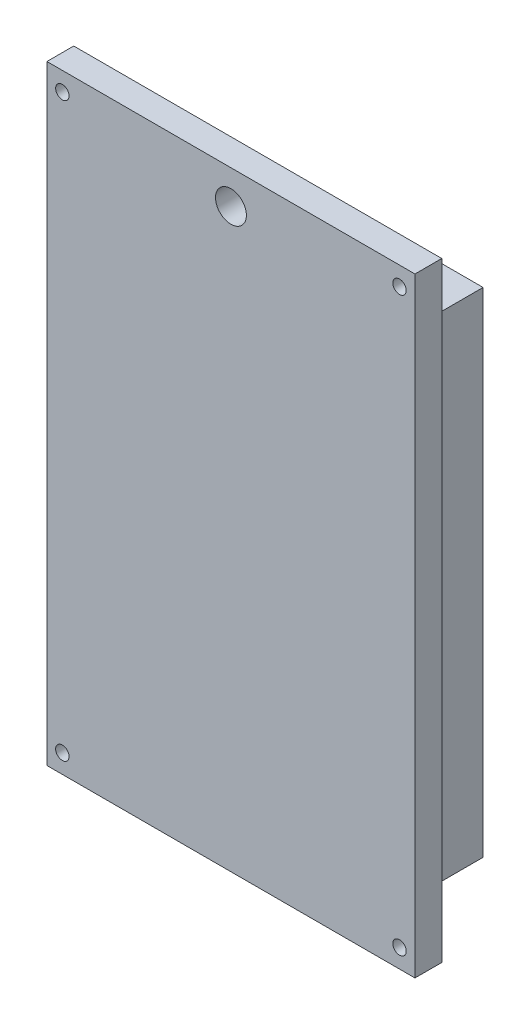
SolidWorks part; units mm, degrees
ref_plane "Front" through (0, 0, 0) normal (0, 0, 1) x (1, 0, 0)
ref_plane "Top" through (0, 0, 0) normal (0, 1, 0) x (1, 0, 0)
ref_plane "Right" through (0, 0, 0) normal (1, 0, 0) x (0, 0, -1)
sketch "arduinoOutline" plane through (0, 0, 0) normal (0, 0, 1) x (1, 0, 0)
  line L0 (0, 32.73) -> (2.54, 35.27) construction
  line L2 (0, 0) -> (0, 32.73) construction
  line L5 (2.54, 35.27) -> (2.54, 36.81) construction
  line L6 (3.54, 37.81) -> (67.6, 37.81) construction
  line L7 (68.6, 36.81) -> (68.6, -14.59) construction
  line L8 (67.6, -15.59) -> (4.06, -15.59) construction
  line L9 (4.06, -15.59) -> (2.54, -14.07) construction
  line L10 (2.54, -14.07) -> (2.54, -2.54) construction
  line L11 (2.54, -2.54) -> (0, 0) construction
  arc A0 (2.54, 36.81) -> (3.54, 37.81) centre (3.54, 36.81) cw construction
  arc A1 (68.6, -14.59) -> (67.6, -15.59) centre (67.6, -14.59) cw construction
  arc A2 (67.6, 37.81) -> (68.6, 36.81) centre (67.6, 36.81) cw construction
  point P8 (2.54, 37.81)
  point P13 (68.6, -15.59)
  point P16 (68.6, 37.81)
  dimension "D6" = 1
  dimension "D9" = 1
  dimension "D10" = 1
  dimension "D1" = 32.73
  dimension "D2" = 135
  dimension "D3" = 3.5921
  dimension "D4" = 2.54
  dimension "D5" = 66.06
  dimension "D7" = 53.4
  dimension "D8" = 64.54
  dimension "D11" = 135
  dimension "D12" = 2.1496
  dimension "D13" = 11.53
  dimension "D14" = 135
  dimension "D15" = 3.5921
sketch "arduinoMountingHolesSketch" plane through (0, 0, 0) normal (0, 0, 1) x (1, 0, 0)
  line L0 (0, 0) -> (0, 32.73) construction
  line L1 (67.6, -15.59) -> (4.06, -15.59) construction
  line L2 (3.54, 37.81) -> (67.6, 37.81) construction
  line L3 (68.6, 36.81) -> (68.6, -14.59) construction
  circle A0 centre (2.54, 2.28) radius 1.25
  circle A1 centre (2.54, 30.45) radius 1.25
  circle A2 centre (54.6, 35.27) radius 1.25
  circle A3 centre (53.35, -13.05) radius 1.25
  dimension "D9" = 2.5
  dimension "D1" = 2.54
  dimension "D2" = 17.87
  dimension "D3" = 2.54
  dimension "D4" = 7.36
  dimension "D5" = 2.54
  dimension "D6" = 14
  dimension "D7" = 2.54
  dimension "D8" = 15.25
sketch "9VbatteryMountingHolesSketch" plane through (0, 0, 0) normal (0, 0, 1) x (1, 0, 0)
  line L0 (0, 16.365) -> (68.6, 16.365) construction
  line L1 (4.875, 40.31) -> (63.725, 40.31) construction
  line L2 (4.875, 40.31) -> (4.875, 88.56) construction
  line L3 (4.875, 88.56) -> (63.725, 88.56) construction
  line L4 (63.725, 40.31) -> (63.725, 88.56) construction
  line L5 (0, 0) -> (0, 32.73) construction
  line L6 (68.6, 36.81) -> (68.6, -14.59) construction
  line L7 (34.3, 40.31) -> (34.3, 88.56) construction
  line L8 (4.875, 64.435) -> (63.725, 64.435) construction
  line L10 (3.54, 37.81) -> (67.6, 37.81) construction
  circle A0 centre (8.625, 86.06) radius 1.25
  circle A1 centre (59.975, 86.06) radius 1.25
  circle A2 centre (8.625, 42.81) radius 1.25
  circle A3 centre (59.975, 42.81) radius 1.25
  point P4 (34.3, 16.365)
  point P5 (34.3, 88.56)
  dimension "D3" = 2.5
  dimension "D1" = 48.25
  dimension "D2" = 58.85
  dimension "D4" = 2.5
  dimension "D5" = 3.75
  dimension "D6" = 2.5
sketch "legBracketMountingHolesSketch" plane through (0, 0, 0) normal (0, 0, 1) x (1, 0, 0)
  line L0 (34.3, 91.06) -> (34.3, 98.06) construction
  line L1 (24.1051, 98.06) -> (44.4949, 98.06) construction
  line L2 (24.1051, 98.06) -> (24.1051, 91.06) construction
  line L3 (24.1051, 91.06) -> (44.4949, 91.06) construction
  line L4 (44.4949, 98.06) -> (44.4949, 91.06) construction
  circle A0 centre (29.2026, 94.56) radius 2
  circle A1 centre (39.3974, 94.56) radius 2
  point P4 (24.1051, 94.56)
  point P5 (34.3, 98.06)
  dimension "D4" = 4
  dimension "D1" = 7
  dimension "D2" = 20.3898
  dimension "D3" = 2.5
  dimension "D5" = 5.0974
sketch "backsideMountingHolesSketch" plane through (0, 0, 0) normal (0, 0, 1) x (1, 0, 0)
  line L0 (0, 41.235) -> (68.6, 41.235) construction
  line L9 (0, 0) -> (0, 32.73) construction
  line L10 (34.3, 40.31) -> (34.3, 88.56) construction
  line L11 (68.6, 36.81) -> (68.6, -14.59) construction
  line L12 (24.1051, 98.06) -> (44.4949, 98.06) construction
  line L13 (4.875, 88.56) -> (63.725, 88.56) construction
  line L14 (4.875, 40.31) -> (4.875, 88.56) construction
  circle A1 centre (2.875, 94.56) radius 1.25
  circle A5 centre (65.725, 94.56) radius 1.25
  circle A6 centre (65.725, -12.09) radius 1.25
  circle A7 centre (2.875, -12.09) radius 1.25
  dimension "D1" = 2.5
  dimension "D2" = 56.825
  dimension "D3" = 6
  dimension "D4" = 2
sketch "Sketch1" plane through (0, 0, 0) normal (0, 0, 1) x (1, 0, 0)
  line L0 (67.6, -15.59) -> (4.06, -15.59) construction
  line L1 (0, 98.06) -> (68.6, 98.06)
  line L2 (0, 98.06) -> (0, -15.59)
  line L3 (0, -15.59) -> (68.6, -15.59)
  line L4 (68.6, 98.06) -> (68.6, -15.59)
  line L5 (0, 0) -> (0, 32.73) construction
  line L6 (68.6, 36.81) -> (68.6, -14.59) construction
  line L9 (24.1051, 98.06) -> (44.4949, 98.06) construction
extrude "bracketBase" add sketch "Sketch1" along normal blind 5
extrude "arduinoMountingHoles" cut sketch "arduinoMountingHolesSketch" against normal through all and the other way blind 22
extrude "9VbatteryMountingHoles" cut sketch "9VbatteryMountingHolesSketch" along normal blind 20
extrude "legBracketMountingHoles" cut sketch "legBracketMountingHolesSketch" along normal blind 13
extrude "backsideMountingHoles" cut sketch "backsideMountingHolesSketch" along normal blind 24
sketch "Sketch2" plane through (0, 0, 5) normal (0, 0, 1) x (1, 0, 0)
  circle A0 centre (53.35, -13.05) radius 1.25 construction
  circle A1 centre (2.54, 2.28) radius 1.25 construction
  circle A2 centre (2.54, 30.45) radius 1.25 construction
  circle A3 centre (54.6, 35.27) radius 1.25 construction
  circle A4 centre (59.975, 42.81) radius 1.25 construction
  circle A5 centre (8.625, 42.81) radius 1.25 construction
  circle A6 centre (59.975, 86.06) radius 1.25 construction
  circle A7 centre (39.3974, 94.56) radius 2 construction
  circle A8 centre (29.2026, 94.56) radius 2 construction
  circle A9 centre (8.625, 86.06) radius 1.25 construction
  circle A10 centre (53.35, -13.05) radius 1.25
  circle A11 centre (2.54, 2.28) radius 1.25
  circle A12 centre (2.54, 30.45) radius 1.25
  circle A13 centre (54.6, 35.27) radius 1.25
  circle A14 centre (59.975, 42.81) radius 1.25
  circle A15 centre (8.625, 42.81) radius 1.25
  circle A16 centre (59.975, 86.06) radius 1.25
  circle A17 centre (39.3974, 94.56) radius 2
  circle A18 centre (29.2026, 94.56) radius 2
  circle A19 centre (8.625, 86.06) radius 1.25
extrude "cover" add sketch "Sketch2" against normal up to surface (5 mm away) up to face at (1.625, -12.09, 0)
sketch "Sketch3" plane through (0, 0, 5) normal (0, 0, 1) x (1, 0, 0)
  line L1 (68.6, 98.06) -> (0, 98.06) construction
  line L2 (0, 98.06) -> (0, -15.59) construction
  line L3 (2.3, -4.765) -> (2.3, 87.235)
  line L4 (5.3, -1.765) -> (63.3, -1.765)
  line L5 (5.3, -1.765) -> (5.3, 84.235)
  line L6 (5.3, 84.235) -> (63.3, 84.235)
  line L7 (63.3, -1.765) -> (63.3, 84.235)
  line L8 (5.3, -1.765) -> (63.3, 84.235) construction
  line L9 (5.3, 84.235) -> (63.3, -1.765) construction
  line L10 (2.3, 87.235) -> (66.3, 87.235)
  line L11 (66.3, -4.765) -> (66.3, 87.235)
  line L12 (2.3, -4.765) -> (66.3, -4.765)
  point P4 (34.3, 98.06)
  point P5 (0, 41.235)
  point P6 (34.3, 41.235)
  dimension "D1" = 86
  dimension "D2" = 58
  dimension "D3" = 3
extrude "breadBoardCavity" add sketch "Sketch3" along normal blind 10
ref_plane "Plane1" through (0, 0, 2.5) normal (0, 0, 1) x (1, 0, 0)
mirror "Mirror1" about plane through (0, 0, 2.5) normal (0, 0, 1) of "breadBoardCavity"
sketch "Sketch4" plane through (0, 87.235, 0) normal (0, 1, 0) x (1, 0, 0)
  line L4 (66.3, -5) -> (2.3, -5)
  line L5 (2.3, -5) -> (2.3, -15)
  line L6 (2.3, -15) -> (66.3, -15)
  line L7 (66.3, -15) -> (66.3, -5)
  line L8 (66.3, -5) -> (2.3, -5)
  line L9 (2.3, -5) -> (2.3, -15)
  line L10 (2.3, -15) -> (66.3, -15)
  line L11 (66.3, -15) -> (66.3, -5)
  dimension "D1" = 0
extrude "Cut-Extrude1" cut sketch "Sketch4" against normal through all
sketch "Sketch5" plane through (0, 0, 0) normal (0, 0, -1) x (-1, 0, 0)
  line L0 (-66.3, 87.235) -> (-2.3, 87.235) construction
  line L1 (-68.6, 98.06) -> (0, 98.06) construction
  circle A0 centre (-34.3, 91.81) radius 2.875
  point P2 (-34.3, 98.06)
  point P9 (-34.3, 94.685)
  dimension "D1" = 5.75
  dimension "D2" = 4.575
extrude "toggleSwitchHole" cut sketch "Sketch5" against normal blind 10
equation "\"D2@backsideMountingHolesSketch\"=113.65mm/2"
